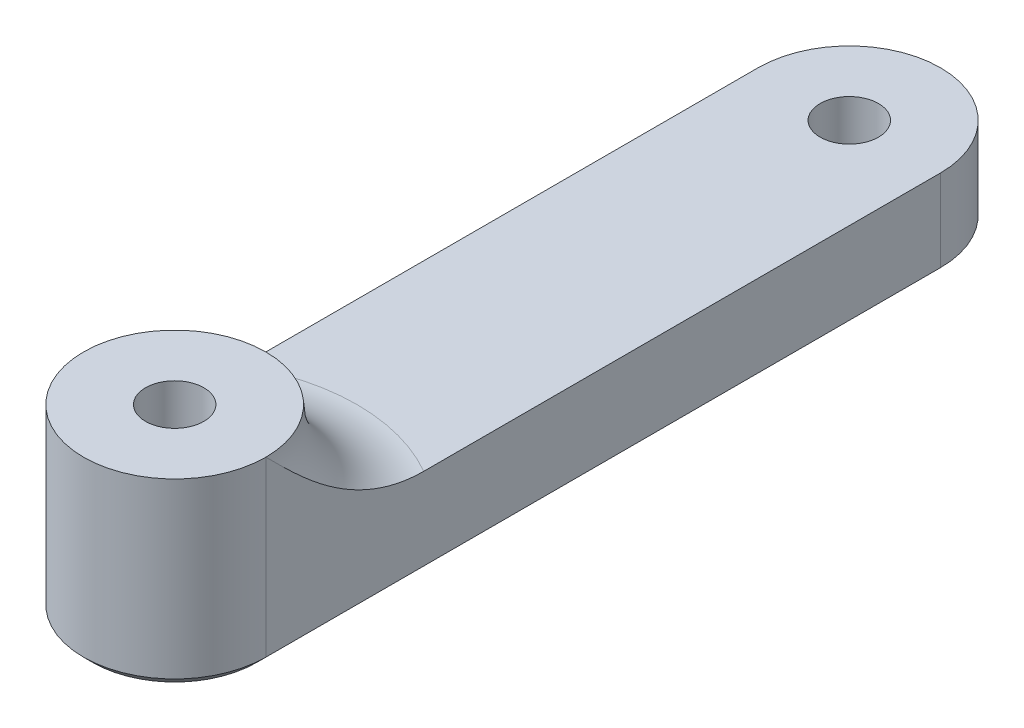
SolidWorks part; units mm, degrees
ref_plane "Front Plane" through (0, 0, 0) normal (0, 0, 1) x (1, 0, 0)
ref_plane "Top Plane" through (0, 0, 0) normal (0, 1, 0) x (1, 0, 0)
ref_plane "Right Plane" through (0, 0, 0) normal (1, 0, 0) x (0, 0, -1)
sketch "complete_sketch" plane through (0, 0, 0) normal (0, 1, 0) x (1, 0, 0)
  line L0 (0, 0) -> (0, 37) construction
  line L1 (-5, 0) -> (-5, 37)
  line L2 (5, 0) -> (5, 37)
  arc A0 (-5, 0) -> (5, 0) centre (0, 0) ccw
  arc A1 (5, 37) -> (-5, 37) centre (0, 37) ccw
  circle A2 centre (0, 37) radius 1.6
  circle A3 centre (0, 0) radius 1.6
  circle A4 centre (0, 0) radius 5
  point P3 (0, 18.5)
  dimension "D1" = 3.2
  dimension "D2" = 37
  dimension "D3" = 10
extrude "Body" add sketch "complete_sketch" along normal blind 5 contours A4 L2 A1 L1 A2 region at (0, 0, -22.1032)
extrude "rise_platform" add sketch "complete_sketch<3>" along normal blind 10 contours A3 A4 A0 region at (0, 0, -4.8586)
sketch "complete_sketch<3>" plane through (0, 0, 0) normal (0, 1, 0) x (1, 0, 0) same geometry as "complete_sketch"
chamfer "elephantsfoot_compensation" distance 0.5 angle 45 6 edges at (5, 0, -18.5) (0, 0, -42) (-5, 0, -18.5) (0, 0, -35.4) (0, 0, 1.6) (0, 0, 5)
fillet "Fillet1" radius 5 1 edges at (0, 5, -5)
